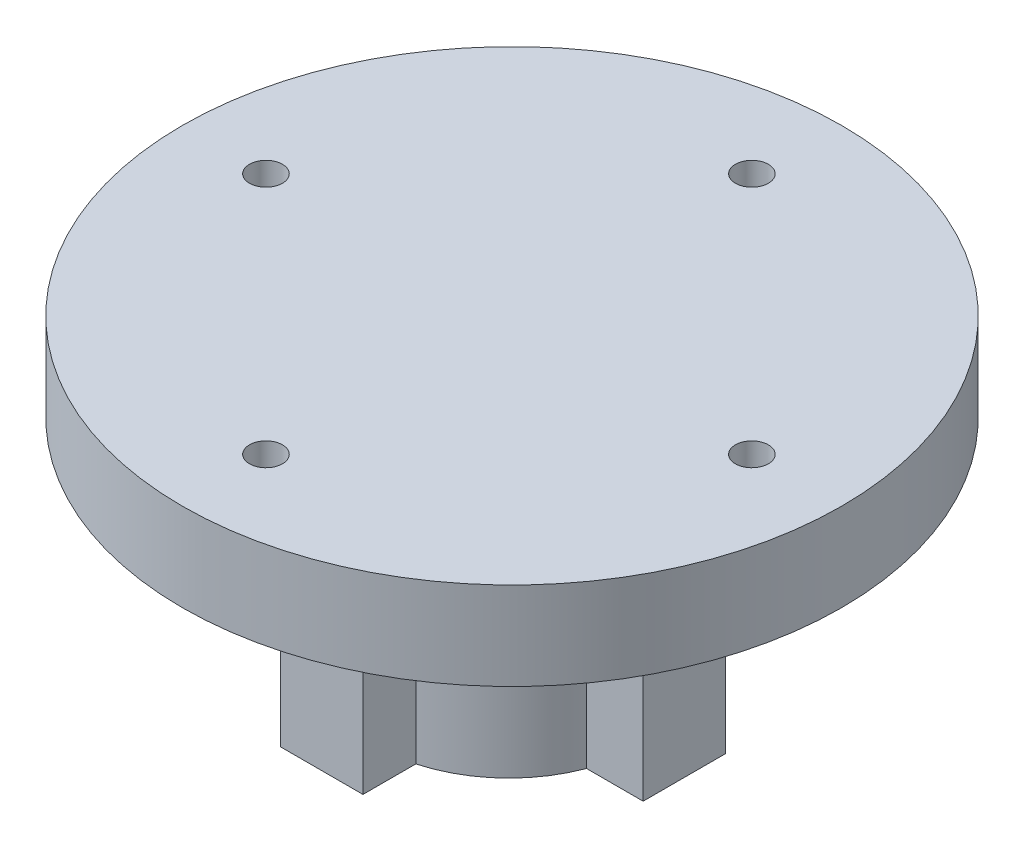
SolidWorks part; units mm, degrees
ref_plane "Front Plane" through (0, 0, 0) normal (0, 0, 1) x (1, 0, 0)
ref_plane "Top Plane" through (0, 0, 0) normal (0, 1, 0) x (1, 0, 0)
ref_plane "Right Plane" through (0, 0, 0) normal (1, 0, 0) x (0, 0, -1)
sketch "Sketch1" plane through (0, 0, 0) normal (0, 1, 0) x (1, 0, 0)
  line L0 (16.4968, 3.2166) -> (16.4968, -4.2834)
  line L1 (-3.2166, 16.4968) -> (4.2834, 16.4968)
  line L2 (-3.2166, 16.4968) -> (-3.2166, 11.6906)
  line L4 (4.2834, 16.4968) -> (4.2834, 11.3432)
  line L5 (-3.2166, 16.4968) -> (-0.0887, 12.1247) construction
  line L6 (-3.2166, 8.9968) -> (4.2834, 16.4968) construction
  line L7 (16.4968, 3.2166) -> (11.6906, 3.2166)
  line L8 (16.4968, -4.2834) -> (11.3432, -4.2834)
  line L9 (3.2166, -16.4968) -> (-4.2834, -16.4968)
  line L10 (3.2166, -16.4968) -> (3.2166, -11.6906)
  line L11 (-4.2834, -16.4968) -> (-4.2834, -11.3432)
  line L12 (-16.4968, -3.2166) -> (-16.4968, 4.2834)
  line L13 (-16.4968, -3.2166) -> (-11.6906, -3.2166)
  line L14 (-16.4968, 4.2834) -> (-11.3432, 4.2834)
  arc A0 (-3.2166, 11.6906) -> (-11.3432, 4.2834) centre (0, 0) ccw
  arc A1 (-11.6906, -3.2166) -> (-4.2834, -11.3432) centre (0, 0) ccw
  arc A2 (3.2166, -11.6906) -> (11.3432, -4.2834) centre (0, 0) ccw
  arc A3 (11.6906, 3.2166) -> (4.2834, 11.3432) centre (0, 0) ccw
  point P3 (-0.0887, 12.1247)
  point P25 (0, 0)
  dimension "D1" = 24.25
  dimension "D2" = 7.5
  dimension "D3" = 7.5
  dimension "D4" = 4
extrude "Boss-Extrude1" add sketch "Sketch1" along normal blind 20
sketch "Sketch2" plane through (0, 20, 0) normal (0, 1, 0) x (1, 0, 0)
  circle A0 centre (0.28, 0) radius 30
  dimension "D1" = 60
extrude "Boss-Extrude2" add sketch "Sketch2" along normal blind 8
sketch "Sketch3" plane through (0, 28, 0) normal (0, 1, 0) x (1, 0, 0)
  circle A0 centre (0, 22.1067) radius 1.5
  circle A1 centre (22.1067, 0) radius 1.5
  circle A2 centre (0, -22.1067) radius 1.5
  circle A3 centre (-22.1067, 0) radius 1.5
  point P11 (0, 0)
  dimension "D1" = 4
extrude "Cut-Extrude1" cut sketch "Sketch3" against normal blind 12
